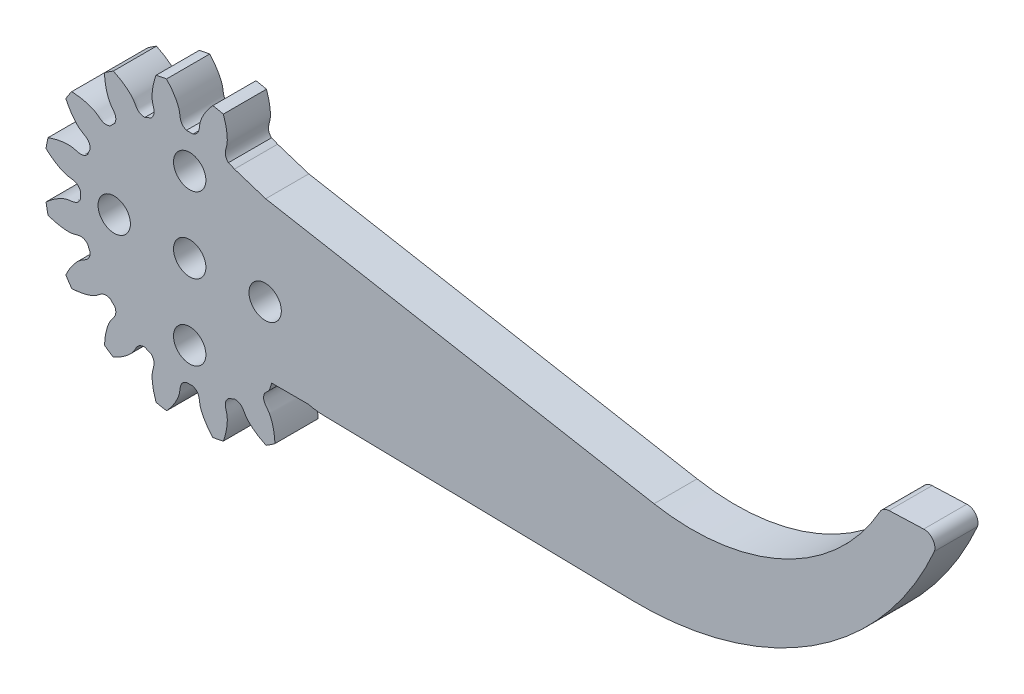
SolidWorks part; units mm, degrees
material "Thornel Mat VMA"
ref_plane "前视基准面" through (0, 0, 0) normal (0, 0, 1) x (1, 0, 0)
ref_plane "上视基准面" through (0, 0, 0) normal (0, 1, 0) x (1, 0, 0)
ref_plane "右视基准面" through (0, 0, 0) normal (1, 0, 0) x (0, 0, -1)
other "Configuration Table"
sketch "草图1" plane through (0, 0, 0) normal (0, 0, 1) x (1, 0, 0)
  circle A0 centre (0, 0) radius 13.5
extrude "凸台-拉伸1" add sketch "草图1" along normal blind 4
ref_axis "基准轴1" through (0, 0, -1.5) along (0, 0, 1)
sketch "草图2" plane through (0, 0, 0) normal (0, 0, 1) x (1, 0, 0)
  line L0 (0, 0) -> (0, 13.5) construction
  circle A0 centre (0, 0) radius 13.5 construction
  arc A1 (0.305, 10.1204) -> (-0.305, 10.1204) centre (0, 0) ccw
  arc A2 (4.6827, 15.2441) -> (-4.6827, 15.2441) centre (0, 0) ccw
  spline S0 degree 3 poles (0.305, 10.1204) (0.9628, 10.3952) (0.854, 10.906) (0.9672, 11.3802) (0.9768, 11.4173) (0.9884, 11.4586) (1.0021, 11.5039) (1.0181, 11.5533) (1.0366, 11.6065) (1.0577, 11.6636) (1.0816, 11.7245) (1.1084, 11.7891) (1.1383, 11.8573) (1.1715, 11.9289) (1.2081, 12.0039) (1.2482, 12.0822) (1.292, 12.1636) (1.3397, 12.2481) (1.3913, 12.3354) (1.447, 12.4256) (1.507, 12.5184) (1.5714, 12.6138) (1.6402, 12.7115) (1.7136, 12.8115) (1.7918, 12.9135) (1.8748, 13.0175) (1.9628, 13.1233) (2.0558, 13.2307) (2.1539, 13.3396) (2.2573, 13.4498) (2.366, 13.5612) (2.4802, 13.6735) (2.5998, 13.7866) (2.7251, 13.9003) (2.856, 14.0144) (2.9925, 14.1288) (3.1349, 14.2433) (3.2831, 14.3577) (3.4372, 14.4717) (3.5972, 14.5853) (3.7632, 14.6982) (3.9352, 14.8102) (4.1132, 14.9211) (4.3612, 15.0689) (4.5525, 15.1751) (4.6827, 15.2441) knots 0 0 0 0 0.200958 0.205848 0.21139 0.217584 0.224431 0.231929 0.240079 0.248881 0.258335 0.268441 0.2792 0.29061 0.302672 0.315386 0.328753 0.342771 0.357441 0.372764 0.388738 0.405364 0.422643 0.440573 0.459155 0.47839 0.498276 0.518814 0.540005 0.561847 0.584342 0.607488 0.631287 0.655737 0.68084 0.706594 0.733001 0.760059 0.78777 0.816132 0.845147 0.874814 0.905132 0.936103 1 1 1 1
  spline S1 degree 3 poles (-0.305, 10.1204) (-0.9628, 10.3952) (-0.854, 10.906) (-0.9672, 11.3802) (-0.9768, 11.4173) (-0.9884, 11.4586) (-1.0021, 11.5039) (-1.0181, 11.5533) (-1.0366, 11.6065) (-1.0577, 11.6636) (-1.0816, 11.7245) (-1.1084, 11.7891) (-1.1383, 11.8573) (-1.1715, 11.9289) (-1.2081, 12.0039) (-1.2482, 12.0822) (-1.292, 12.1636) (-1.3397, 12.2481) (-1.3913, 12.3354) (-1.447, 12.4256) (-1.507, 12.5184) (-1.5714, 12.6138) (-1.6402, 12.7115) (-1.7136, 12.8115) (-1.7918, 12.9135) (-1.8748, 13.0175) (-1.9628, 13.1233) (-2.0558, 13.2307) (-2.1539, 13.3396) (-2.2573, 13.4498) (-2.366, 13.5612) (-2.4802, 13.6735) (-2.5998, 13.7866) (-2.7251, 13.9003) (-2.856, 14.0144) (-2.9925, 14.1288) (-3.1349, 14.2433) (-3.2831, 14.3577) (-3.4372, 14.4717) (-3.5972, 14.5853) (-3.7632, 14.6982) (-3.9352, 14.8102) (-4.1132, 14.9211) (-4.3612, 15.0689) (-4.5525, 15.1751) (-4.6827, 15.2441) knots 0 0 0 0 0.200958 0.205848 0.21139 0.217584 0.224431 0.231929 0.240079 0.248881 0.258335 0.268441 0.2792 0.29061 0.302672 0.315386 0.328753 0.342771 0.357441 0.372764 0.388738 0.405364 0.422643 0.440573 0.459155 0.47839 0.498276 0.518814 0.540005 0.561847 0.584342 0.607488 0.631287 0.655737 0.68084 0.706594 0.733001 0.760059 0.78777 0.816132 0.845147 0.874814 0.905132 0.936103 1 1 1 1
extrude "切除-拉伸1" cut sketch "草图2" along normal through all
pattern_circular "阵列(圆周)1" count 16 every 22.5 about axis through (0, 0, -1.5) along (0, 0, 1) of "切除-拉伸1"
sketch "草图3" plane through (0, 0, 0) normal (0, 0, 1) x (1, 0, 0)
  circle A0 centre (0, 0) radius 12 construction
  dimension "Dn" = 24
sketch "草图4" plane through (0, 0, 4) normal (0, 0, 1) x (1, 0, 0)
  line L0 (0, 0) -> (0, 22.6625) construction
  line L1 (7.0482, 8.2984) -> (0, 0)
  line L4 (43.0675, 1.8094) -> (7.0482, 8.2984)
  line L5 (68.0825, 12.2822) -> (64.8605, 12.1626)
  line L6 (12.4209, -6.4212) -> (41.0243, -6.9675)
  line L7 (0, 0) -> (9.4771, -5.5843)
  arc A3 (9.4771, -5.5843) -> (12.4209, -6.4212) centre (12.5354, -0.4223) ccw
  arc A9 (43.0675, 1.8094) -> (64.0269, 11.6552) centre (46.6135, 21.4925) ccw
  arc A10 (64.8605, 12.1626) -> (64.0269, 11.6552) centre (64.8976, 11.1633) ccw
  arc A11 (69.0741, 10.9847) -> (68.0825, 12.2822) centre (68.1195, 11.2829) ccw
  arc A12 (41.0243, -6.9675) -> (69.0741, 10.9847) centre (41.5971, 23.0271) ccw
  spline S0 degree 3 poles (7.9084, 10.9411) (7.9024, 10.8035) (7.8863, 10.579) (7.8492, 10.2751) (7.8101, 10.0346) (7.7651, 9.8136) (7.7155, 9.6121) (7.663, 9.43) (7.6089, 9.2674) (7.5547, 9.1238) (7.5093, 9.0165) (7.4668, 8.9243) (7.4348, 8.8597) (7.3975, 8.7901) (7.3706, 8.7431) (7.1079, 8.3156) (6.6697, 8.0313) (6.9405, 7.3719) knots 0.46188 0.46188 0.46188 0.46188 0.52161 0.559427 0.594636 0.627236 0.657229 0.684614 0.70939 0.731559 0.751119 0.759921 0.775569 0.782416 0.794152 0.799042 1 1 1 1 construction
  dimension "D1" = 11
extrude "凸台-拉伸2" add sketch "草图4" against normal blind 4
sketch "草图5" plane through (0, 0, 4) normal (0, 0, 1) x (1, 0, 0)
  line L0 (9.9061, 7.7835) -> (11.1899, 7.5522)
  line L1 (7.0482, 8.2984) -> (4.1547, 9.2333)
  line L2 (7.3719, -6.9405) -> (7.6024, -6.2272)
  line L3 (7.6024, -6.2272) -> (11.018, -6.2272)
  arc A0 (11.1899, 7.5522) -> (10.9411, 7.9084) centre (0, 0) ccw construction
  arc A1 (10.9411, -7.9084) -> (11.4934, -7.0818) centre (0, 0) ccw construction
  arc A2 (11.1899, 7.5522) -> (10.9411, 7.9084) centre (0, 0) ccw
  arc A3 (10.9411, -7.9084) -> (11.4934, -7.0818) centre (0, 0) ccw
  arc A4 (7.9084, 10.9411) -> (7.0818, 11.4934) centre (0, 0) ccw construction
  arc A5 (7.9084, 10.9411) -> (7.0818, 11.4934) centre (0, 0) ccw
  spline S0 degree 3 poles (1120.558, -1654.5074) (-8.0515, -79.155) (-7.2393, 4.4551) (10.071, 7.8161) (10.2751, 7.8492) (10.4878, 7.8752) (10.6675, 7.8917) (35.5547, 9.682) (68.358, -117.1707) (-1277.8902, 1537.0142) knots -7.206049 -7.206049 -7.206049 -7.206049 0.388738 0.405364 0.440573 0.47839 0.498276 0.518814 11.298348 11.298348 11.298348 11.298348 only from (9.9061, 7.7835) to (10.9411, 7.9084) construction
  spline S1 degree 3 poles (-1277.9047, -1537.0319) (68.3582, 117.1716) (35.5548, -9.682) (10.6232, -7.8885) (10.4026, -7.8661) (10.1524, -7.8305) (9.9217, -7.7883) (9.7104, -7.7408) (9.5186, -7.6895) (9.3463, -7.636) (9.1932, -7.5817) (9.0592, -7.5281) (8.9597, -7.4836) (8.8751, -7.4426) (8.8051, -7.4061) (8.7431, -7.3706) (3.6661, -4.2504) (17.369, 28.463) (-985.2294, -1742.934) knots -10.298386 -10.298386 -10.298386 -10.298386 0.481186 0.501724 0.540845 0.577357 0.611262 0.642559 0.671247 0.697328 0.7208 0.741665 0.759921 0.768071 0.782416 0.794152 0.799042 3.366499 3.366499 3.366499 3.366499 only from (10.9411, -7.9084) to (7.3719, -6.9405) construction
  spline S2 degree 3 poles (-1113.5381, -1659.1116) (-79.5153, -21.6293) (1.3555, 9.0349) (11.1391, -6.416) (11.2482, -6.6005) (11.3534, -6.7958) (22.5512, -29.1431) (-82.0919, -107.9936) (930.9843, 1768.7986) knots -7.47126 -7.47126 -7.47126 -7.47126 0.405364 0.422643 0.459155 0.498276 0.518814 11.298333 11.298333 11.298333 11.298333 only from (11.018, -6.2272) to (11.4934, -7.0818) construction
  spline S3 degree 3 poles (9.9061, 7.7835) (9.986, 7.8) (10.1491, 7.8301) (10.4026, 7.8661) (10.6675, 7.893) (10.8493, 7.9044) (10.9411, 7.9084) knots 0.387264 0.387264 0.387264 0.387264 0.422643 0.459155 0.498276 0.53812 0.53812 0.53812 0.53812
  spline S4 degree 3 poles (10.9411, -7.9084) (10.8035, -7.9024) (10.579, -7.8863) (10.2751, -7.8492) (10.0346, -7.8101) (9.8136, -7.7651) (9.6121, -7.7155) (9.43, -7.663) (9.2674, -7.6089) (9.1238, -7.5547) (9.0165, -7.5093) (8.9243, -7.4668) (8.8597, -7.4348) (8.7901, -7.3975) (8.7431, -7.3706) (8.3156, -7.1079) (8.0313, -6.6697) (7.3719, -6.9405) knots 0.46188 0.46188 0.46188 0.46188 0.52161 0.559427 0.594636 0.627236 0.657229 0.684614 0.70939 0.731559 0.751119 0.759921 0.775569 0.782416 0.794152 0.799042 1 1 1 1
  spline S5 degree 3 poles (11.018, -6.2272) (11.074, -6.3117) (11.174, -6.4716) (11.3125, -6.717) (11.4152, -6.9172) (11.4745, -7.0415) (11.4934, -7.0818) knots 0.396627 0.396627 0.396627 0.396627 0.440573 0.47839 0.518814 0.53812 0.53812 0.53812 0.53812
  spline S6 degree 3 poles (1537.0114, -1277.888) (-117.1706, 68.358) (9.682, 35.5547) (7.8885, 10.6232) (7.8661, 10.4026) (7.8305, 10.1524) (7.7883, 9.9217) (7.7408, 9.7104) (7.6895, 9.5186) (7.636, 9.3463) (7.5817, 9.1932) (7.5281, 9.0592) (7.4836, 8.9597) (7.4426, 8.8751) (7.4061, 8.8051) (7.3706, 8.7431) (4.2506, 3.6664) (-28.4588, 17.3673) (1742.597, -985.0387) knots -10.298342 -10.298342 -10.298342 -10.298342 0.481186 0.501724 0.540845 0.577357 0.611262 0.642559 0.671247 0.697328 0.7208 0.741665 0.759921 0.768071 0.782416 0.794152 0.799042 3.366336 3.366336 3.366336 3.366336 only from (7.9084, 10.9411) to (7.0482, 8.2984) construction
  spline S7 degree 3 poles (-1577.3628, 1233.3375) (26.9406, -19.6509) (1.7604, 5.3297) (5.257, 10.1554) (5.3006, 10.2119) (5.3644, 10.2879) (5.4433, 10.3747) (5.5383, 10.4712) (5.6501, 10.5762) (5.7797, 10.6884) (5.9278, 10.8066) (6.095, 10.9295) (6.282, 11.0557) (6.4892, 11.1839) (6.6758, 11.2892) (6.8354, 11.3733) (29.1432, 22.5512) (107.9945, -82.093) (-1768.8285, 931.0004) knots -2.366572 -2.366572 -2.366572 -2.366572 0.200958 0.205848 0.217584 0.231929 0.248881 0.268441 0.29061 0.315386 0.342771 0.372764 0.405364 0.440573 0.47839 0.498276 0.518814 11.29839 11.29839 11.29839 11.29839 only from (4.1547, 9.2333) to (7.0818, 11.4934) construction
  spline S8 degree 3 poles (7.9084, 10.9411) (7.9024, 10.8035) (7.8863, 10.579) (7.8492, 10.2751) (7.8101, 10.0346) (7.7651, 9.8136) (7.7155, 9.6121) (7.663, 9.43) (7.6089, 9.2674) (7.5547, 9.1238) (7.5093, 9.0165) (7.4668, 8.9243) (7.4348, 8.8597) (7.3975, 8.7901) (7.3706, 8.7431) (7.2631, 8.5681) (7.143, 8.4332) (7.0482, 8.2984) knots 0.46188 0.46188 0.46188 0.46188 0.52161 0.559427 0.594636 0.627236 0.657229 0.684614 0.70939 0.731559 0.751119 0.759921 0.775569 0.782416 0.794152 0.799042 0.871466 0.871466 0.871466 0.871466
  spline S9 degree 3 poles (4.1547, 9.2333) (4.8675, 9.2355) (4.9625, 9.7491) (5.257, 10.1554) (5.3006, 10.2119) (5.3644, 10.2879) (5.4433, 10.3747) (5.5383, 10.4712) (5.6501, 10.5762) (5.7797, 10.6884) (5.9278, 10.8066) (6.095, 10.9295) (6.282, 11.0557) (6.4892, 11.1839) (6.717, 11.3125) (6.9172, 11.4152) (7.0415, 11.4745) (7.0818, 11.4934) knots 0 0 0 0 0.200958 0.205848 0.217584 0.231929 0.248881 0.268441 0.29061 0.315386 0.342771 0.372764 0.405364 0.440573 0.47839 0.518814 0.53812 0.53812 0.53812 0.53812
extrude "切除-拉伸2" cut sketch "草图5" against normal blind 5
sketch "草图6" plane through (0, 0, 4) normal (0, 0, 1) x (1, 0, 0)
  line L0 (0, 0) -> (0, 16.4393) construction
  line L1 (0, 0) -> (18.078, 0) construction
  circle A0 centre (0, 0) radius 7 construction
  circle A1 centre (0, 7) radius 1.5
  circle A2 centre (7, 0) radius 1.5
  circle A3 centre (0, -7) radius 1.5
  circle A4 centre (-7, 0) radius 1.5
  circle A5 centre (0, 0) radius 1.5
  dimension "D1" = 14
  dimension "D2" = 3
  dimension "D3" = 3
  dimension "D4" = 3
extrude "切除-拉伸3" cut sketch "草图6" against normal blind 5
